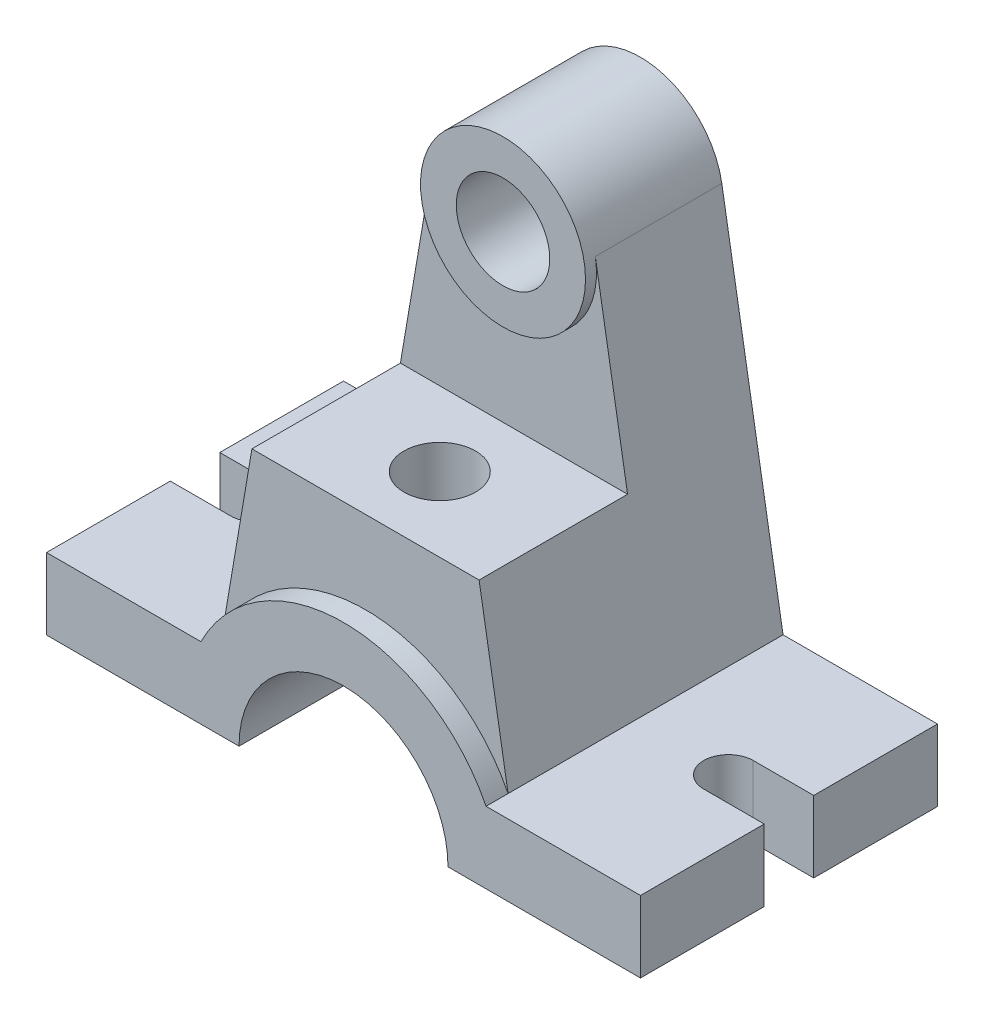
SolidWorks part; units mm, degrees
ref_plane "前视基准面" through (0, 0, 0) normal (0, 0, 1) x (1, 0, 0)
ref_plane "上视基准面" through (0, 0, 0) normal (0, 1, 0) x (1, 0, 0)
ref_plane "右视基准面" through (0, 0, 0) normal (1, 0, 0) x (0, 0, -1)
other "Configuration Table"
sketch "草图1" plane through (0, 0, 0) normal (0, 0, 1) x (1, 0, 0)
  line L0 (0, 104.6405) -> (0, 0) construction
  line L1 (-54, 0) -> (-19, 0)
  line L2 (54, 0) -> (54, 13)
  line L3 (54, 13) -> (25.923, 13)
  line L4 (25.923, 13) -> (14.7879, 78.5134)
  line L5 (-54, 0) -> (-54, 13)
  line L6 (-54, 13) -> (-25.923, 13)
  line L7 (-25.923, 13) -> (-14.7879, 78.5134)
  line L8 (19, 0) -> (54, 0)
  line L9 (-20.654, 44) -> (20.654, 44)
  circle A0 centre (0, 76) radius 15
  arc A1 (19, 0) -> (-19, 0) centre (0, 0) ccw
  arc A2 (25.923, 13) -> (-25.923, 13) centre (0, 0) ccw
  circle A3 centre (0, 76) radius 8.5
  dimension "D4" = 30
  dimension "D5" = 10
  dimension "D3" = 38
  dimension "D6" = 17
  dimension "D1" = 13
  dimension "D2" = 108
  dimension "D7" = 76
  dimension "D8" = 32
extrude "凸台-拉伸1" add sketch "草图1" along normal blind 54 contours A2 L0 A1 L8 L2 L3 | L0 A2 L6 L5 L1 A1 region at (27.5472, 11.305, 0) region at (-27.5472, 11.305, 0)
extrude "凸台-拉伸2" add sketch "草图1<3>" along normal offset from surface (50 mm away) 4 contours L9 L0 A2 L4 | L0 L9 L7 A2 region at (12.7249, 33.7263, 0) region at (-12.7249, 33.7263, 0) up to face at (0, 10.875, 54)
sketch "草图1<3>" plane through (0, 0, 0) normal (0, 0, 1) x (1, 0, 0) same geometry as "草图1"
extrude "凸台-拉伸3" add sketch "草图1<5>" along normal blind 23 contours L0 A0 L7 L9 | A0 L0 L9 L4 region at (10.226, 54.5554, 0) region at (-10.226, 54.5554, 0)
sketch "草图1<5>" plane through (0, 0, 0) normal (0, 0, 1) x (1, 0, 0) same geometry as "草图1"
extrude "凸台-拉伸4" add sketch "草图1<6>" along normal blind 25 contours A0 L0 A3 | L0 A0 A3 region at (9.4609, 87.2046, 0) region at (-0.3354, 87.75, 0)
sketch "草图1<6>" plane through (0, 0, 0) normal (0, 0, 1) x (1, 0, 0) same geometry as "草图1"
sketch "草图2" plane through (0, 44, 0) normal (0, 1, 0) x (1, 0, 0)
  line L0 (-20.654, -36.5) -> (20.654, -36.5) construction
  line L1 (-20.654, -50) -> (-20.654, -23) construction
  line L2 (20.654, -50) -> (20.654, -23) construction
  circle A0 centre (0, -36.5) radius 6.5
  point P8 (0, 0)
  dimension "D1" = 13
extrude "切除-拉伸1" cut sketch "草图2" against normal up to next
sketch "草图3" plane through (0, 13, 0) normal (0, 1, 0) x (1, 0, 0)
  line L0 (0, 0) -> (0, -60.3059) construction
  line L1 (-54, -27) -> (-41.9947, -27) construction
  line L2 (-54, -54) -> (-54, 0) construction
  line L3 (-43, -22.5) -> (-54, -22.5)
  line L4 (-43, -31.5) -> (-54, -31.5)
  line L5 (-54, -22.5) -> (-54, -31.5)
  line L6 (54, -27) -> (41.9947, -27) construction
  line L7 (54, -22.5) -> (54, -31.5)
  line L8 (43, -31.5) -> (54, -31.5)
  line L9 (43, -22.5) -> (54, -22.5)
  arc A0 (-43, -31.5) -> (-43, -22.5) centre (-43, -27) ccw
  arc A1 (43, -31.5) -> (43, -22.5) centre (43, -27) cw
  dimension "D1" = 9
  dimension "D2" = 86
extrude "切除-拉伸2" cut sketch "草图3" against normal up to next
